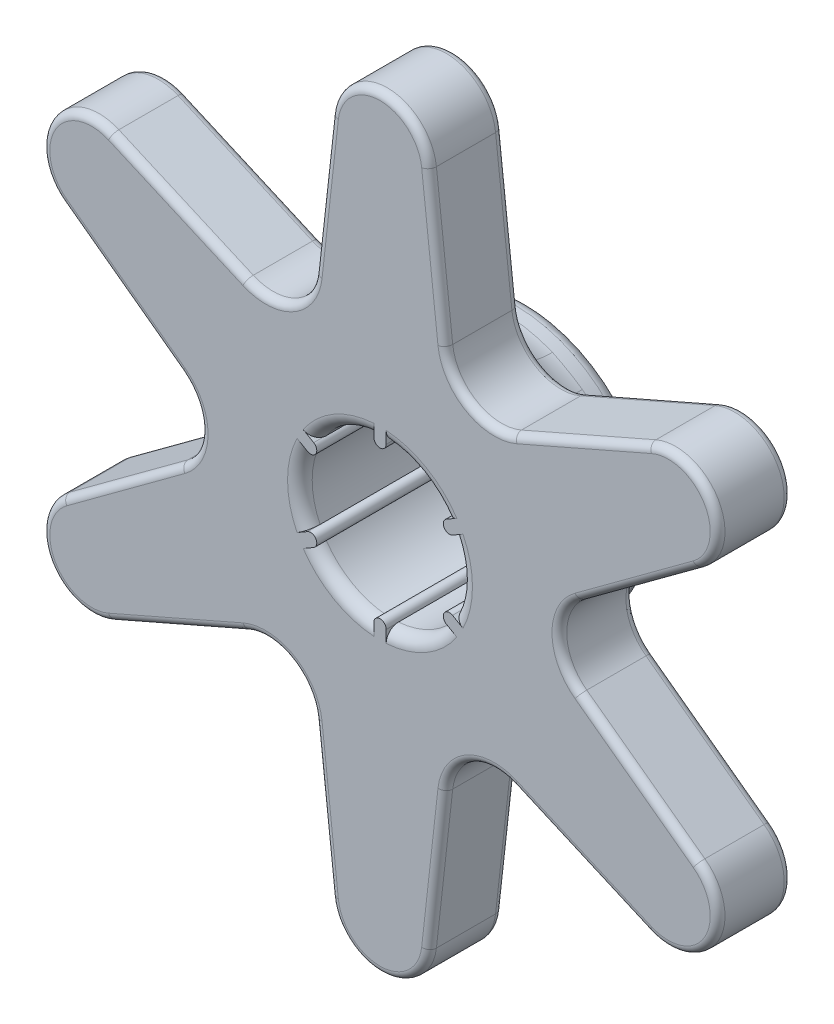
SolidWorks part; units mm, degrees
ref_plane "Front Plane" through (0, 0, 0) normal (0, 0, 1) x (1, 0, 0)
ref_plane "Top Plane" through (0, 0, 0) normal (0, 1, 0) x (1, 0, 0)
ref_plane "Right Plane" through (0, 0, 0) normal (1, 0, 0) x (0, 0, -1)
sketch "Sketch1" plane through (0, 0, 0) normal (0, 0, 1) x (1, 0, 0)
  line L0 (-3.4783, 0.3889) -> (-1.9876, 13.7222)
  line L1 (-3.5, -15.5) -> (3.5, -15.5) construction
  line L2 (-3.5, -15.5) -> (-3.5, 15.5) construction
  line L3 (-3.5, 15.5) -> (3.5, 15.5) construction
  line L4 (3.5, -15.5) -> (3.5, 15.5) construction
  line L5 (-3.5, -15.5) -> (3.5, 15.5) construction
  line L6 (-3.5, 15.5) -> (3.5, -15.5) construction
  line L7 (3.4783, 0.3889) -> (1.9876, 13.7222)
  line L8 (-3.4783, -0.3889) -> (-1.9876, -13.7222)
  line L9 (1.9876, -13.7222) -> (3.4783, -0.3889)
  circle A0 centre (0, 0) radius 3.5
  circle A1 centre (0, 13.5) radius 2
  circle A2 centre (0, -13.5) radius 2
  point P0 (0, 0)
  dimension "D3" = 4
  dimension "D1" = 7
  dimension "D2" = 31
extrude "Boss-Extrude1" add sketch "Sketch1" along normal blind 3 contours A1 L0 A0 L7 | A0 | A2 L9 A0 L8 | A1 | A2 region at (0, 7.1247, 0) region at (0, 0, 0) region at (0, -7.1247, 0)
ref_axis "Axis1" through (0, 0, 0) along (0, 0, 1)
pattern_circular "CirPattern1" count 6 over 360 about axis through (0, 0, 0) along (0, 0, 1) of "Boss-Extrude1"
fillet "Fillet1" radius 2 6 edges at (-2.9505, 5.1103, 1.5) (-5.9009, 0, 1.5) (-2.9505, -5.1103, 1.5) (2.9505, -5.1103, 1.5) (2.9505, 5.1103, 1.5) (5.9009, 0, 1.5)
fillet "Fillet2" radius 0.3 48 edges at (-7.2729, 0, 0) (-10.4821, 3.375, 0) (-13.4234, 7.75, 0) (-8.1639, 7.3903, 0) (-3.6364, 6.2985, 0) (-2.3182, 10.7653, 0) (0, 15.5, 0) (2.3182, 10.7653, 0) (3.6364, 6.2985, 0) (8.1639, 7.3903, 0) (13.4234, 7.75, 0) (10.4821, 3.375, 0) (7.2729, 0, 0) (10.4821, -3.375, 0) (13.4234, -7.75, 0) (8.1639, -7.3903, 0) (3.6364, -6.2985, 0) (2.3182, -10.7653, 0) (0, -15.5, 0) (-2.3182, -10.7653, 0) (-3.6364, -6.2985, 0) (-8.1639, -7.3903, 0) (-13.4234, -7.75, 0) (-7.2729, 0, 3) (-10.4821, 3.375, 3) (-13.4234, 7.75, 3) (-8.1639, 7.3903, 3) (-3.6364, 6.2985, 3) (-2.3182, 10.7653, 3) (0, 15.5, 3) (2.3182, 10.7653, 3) (3.6364, 6.2985, 3) (8.1639, 7.3903, 3) (13.4234, 7.75, 3) (10.4821, 3.375, 3) (7.2729, 0, 3) (10.4821, -3.375, 3) (13.4234, -7.75, 3) (8.1639, -7.3903, 3) (3.6364, -6.2985, 3) (2.3182, -10.7653, 3) (0, -15.5, 3) (-2.3182, -10.7653, 3) (-3.6364, -6.2985, 3) (-8.1639, -7.3903, 3) (-13.4234, -7.75, 3) (-10.4821, -3.375, 0) (-10.4821, -3.375, 3)
sketch "Sketch2" plane through (0, 0, 0) normal (0, 0, -1) x (-1, 0, 0)
  circle A0 centre (0, 0) radius 5.25
  circle A1 centre (0, 0) radius 3.25
  dimension "D2" = 6.5
  dimension "D1" = 2
extrude "Boss-Extrude2" add sketch "Sketch2" along normal blind 3
sketch "Sketch3" plane through (0, 0, 0) normal (0, 0, -1) x (-1, 0, 0)
  circle A1 centre (0, 0) radius 3.25
  circle A2 centre (0, 0) radius 3.25
  dimension "D1" = 0
extrude "Cut-Extrude1" cut sketch "Sketch3" against normal through all
fillet "Fillet3" radius 2 1 edges at (5.25, 0, 0)
fillet "Fillet4" radius 0.5 3 edges at (-3.25, 0, -3) (-5.25, 0, -3) (-3.25, 0, 3)
sketch "Sketch4" plane through (0, 0, -3) normal (0, 0, -1) x (-1, 0, 0)
  line L0 (0, -3.25) -> (0, -4) construction
  line L1 (-0.25, -3.25) -> (-0.25, -4)
  line L2 (0.25, -3.25) -> (0.25, -4)
  circle A0 centre (0, 0) radius 3.25 construction
  arc A1 (-0.25, -3.25) -> (0.25, -3.25) centre (0, -3.25) cw
  arc A2 (-0.25, -4) -> (0.25, -4) centre (0, -4) ccw
  dimension "D3" = 0.75
  dimension "D1" = 0.25
  dimension "D2" = 0.25
extrude "Boss-Extrude3" add sketch "Sketch4" against normal up to surface (6 mm away) up to face at (3.75, 0, 3)
pattern_circular "CirPattern2" count 6 over 360 about axis through (0, 0, -3) along (0, 0, 1) of "Boss-Extrude3"
fillet "Fillet5" radius 0.2 18 edges at (-3.1525, 1.5314, -3) (-2.5981, 1.5, -3) (-2.9025, 1.9644, -3) (-0.25, 3.4958, -3) (0, 3, -3) (0.25, 3.4958, -3) (2.9025, 1.9644, -3) (2.5981, 1.5, -3) (3.1525, 1.5314, -3) (3.1525, -1.5314, -3) (2.5981, -1.5, -3) (2.9025, -1.9644, -3) (0.25, -3.4958, -3) (0, -3, -3) (-0.25, -3.4958, -3) (-2.9025, -1.9644, -3) (-2.5981, -1.5, -3) (-3.1525, -1.5314, -3)
